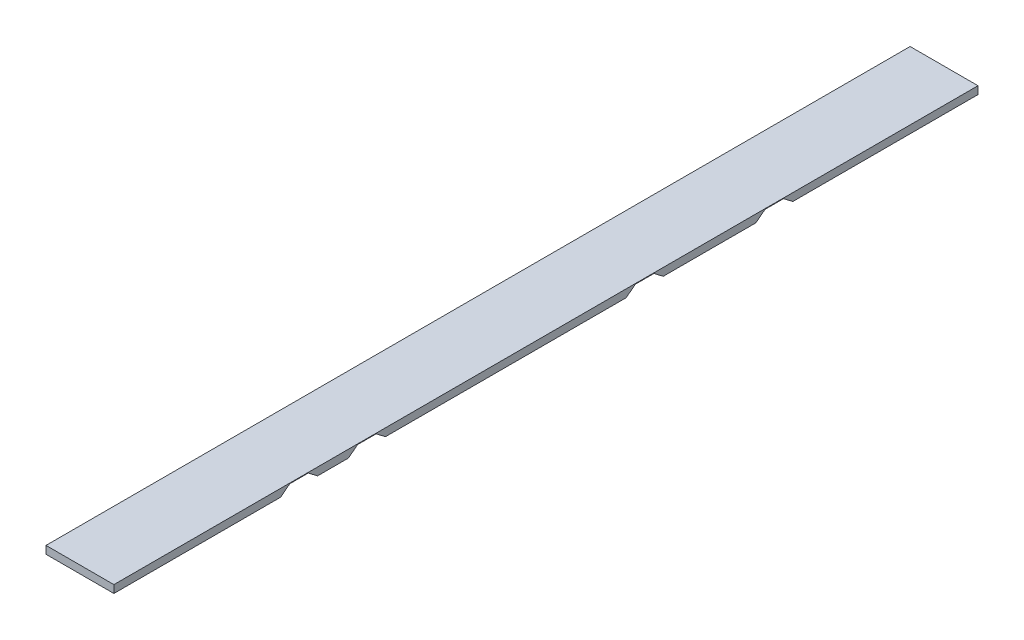
SolidWorks part; units mm, degrees
ref_plane "Front Plane" through (0, 0, 0) normal (0, 0, 1) x (1, 0, 0)
ref_plane "Top Plane" through (0, 0, 0) normal (0, 1, 0) x (1, 0, 0)
ref_plane "Right Plane" through (0, 0, 0) normal (1, 0, 0) x (0, 0, -1)
sketch "Sketch1" plane through (0, 0, 0) normal (1, 0, 0) x (0, 0, -1)
  line L17 (1400, 0) -> (1400, 12.5)
  line L18 (1400, 12.5) -> (0, 12.5)
  line L19 (0, 12.5) -> (0, 0)
  line L20 (0, 0) -> (270, 0)
  line L21 (270, 0) -> (285, 11.5)
  line L22 (285, 11.5) -> (315, 11.5)
  line L23 (315, 11.5) -> (330, 0)
  line L24 (330, 0) -> (380, 0)
  line L25 (380, 0) -> (395, 11.5)
  line L26 (395, 11.5) -> (425, 11.5)
  line L27 (425, 11.5) -> (440, 0)
  line L28 (440, 0) -> (830, 0)
  line L29 (830, 0) -> (845, 11.5)
  line L30 (845, 11.5) -> (875, 11.5)
  line L31 (875, 11.5) -> (890, 0)
  line L32 (890, 0) -> (1040, 0)
  line L33 (1040, 0) -> (1055, 11.5)
  line L34 (1055, 11.5) -> (1085, 11.5)
  line L35 (1085, 11.5) -> (1100, 0)
  line L36 (1100, 0) -> (1400, 0)
  point P13 (926.6773, 2.5)
  point P22 (0, 0)
  point P23 (920.855, 6.883)
  point P24 (920.6913, 3.4453)
  point P25 (349.7975, 0)
  point P26 (263.9921, 0)
  point P27 (202.1004, 0)
  point P28 (140.1686, 0)
  point P29 (876.0325, 3.4453)
  point P30 (677.2157, 0)
  point P31 (631.6143, 0)
  point P32 (1061.5416, -3.3893)
  point P33 (980.976, 0)
  point P34 (475.8381, 0)
  point P35 (402.2889, 0)
  point P36 (260.6169, 0)
  point P37 (225.6322, 0)
  point P38 (450.8461, 12.5)
  point P39 (432.7513, 0)
  point P40 (464.6084, 11.5)
  point P41 (454.669, 12.5)
  point P42 (259.306, 11.5)
  point P43 (388.8167, 11.5)
  point P44 (436.0538, 11.5)
  point P45 (443.1163, 0)
  point P46 (388.8167, 11.5)
  point P47 (391.6038, 11.5)
  dimension "D1" = 12.5
  dimension "D4" = 1400
  dimension "D2" = 1
  dimension "D3" = 60
  dimension "D6" = 60
  dimension "D7" = 60
  dimension "D9" = 270
  dimension "D8" = 15
  dimension "D10" = 15
  dimension "D11" = 50
  dimension "D5" = 15
  dimension "D12" = 15
  dimension "D13" = 60
  dimension "D14" = 390
  dimension "D15" = 15
  dimension "D16" = 15
  dimension "D17" = 15
  dimension "D18" = 15
  dimension "D19" = 150
extrude "Boss-Extrude1" add sketch "Sketch1" along normal blind 110 contours L18 L19 L20 L21 L22 L23 L24 L25 L26 L27 L28 L29 L30 L31 L32 L33 L34 L35 L36 L17
equation "\"D6@Sketch1\"=\"D3@Sketch1\""
equation "\"D7@Sketch1\"=\"D3@Sketch1\""
equation "\"D10@Sketch1\"=\"D8@Sketch1\""
equation "\"D5@Sketch1\"=\"D8@Sketch1\""
equation "\"D12@Sketch1\"=\"D8@Sketch1\""
